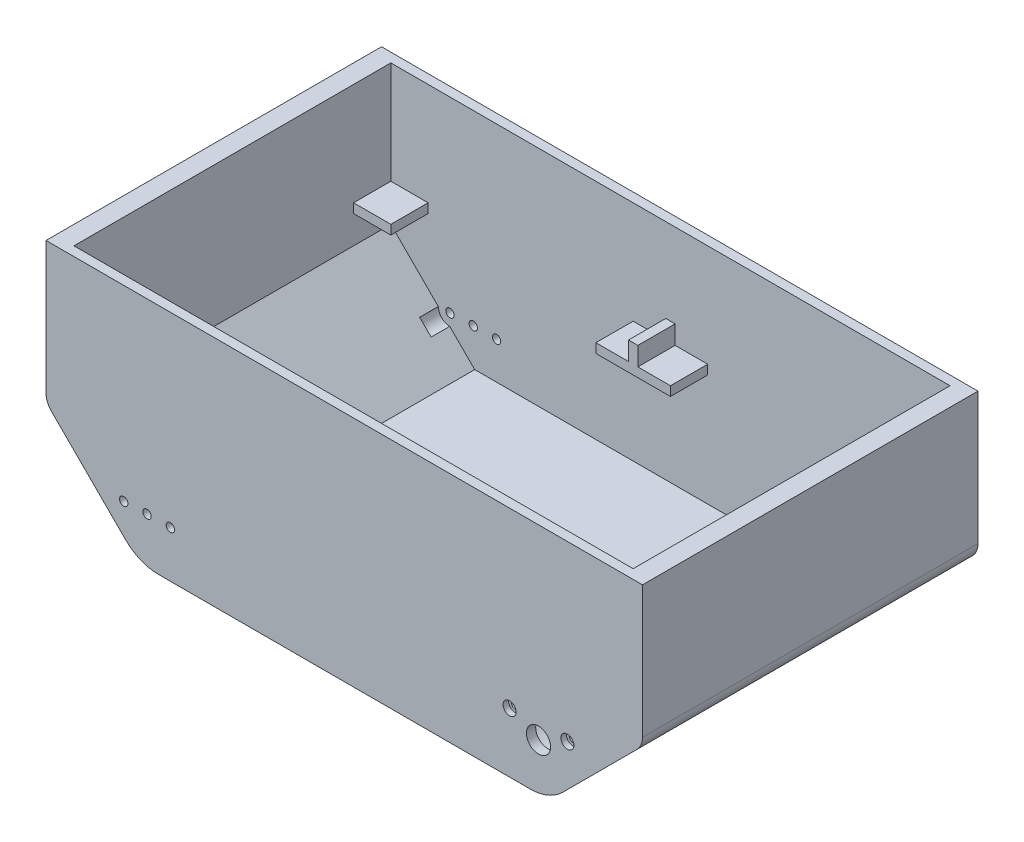
SolidWorks part; units mm, degrees
ref_plane "Front Plane" through (0, 0, 0) normal (0, 0, 1) x (1, 0, 0)
ref_plane "Top Plane" through (0, 0, 0) normal (0, 1, 0) x (1, 0, 0)
ref_plane "Right Plane" through (0, 0, 0) normal (1, 0, 0) x (0, 0, -1)
sketch "Sketch1" plane through (0, 0, 0) normal (0, 1, 0) x (1, 0, 0)
  line L1 (-160, -90) -> (160, -90)
  line L2 (-160, -90) -> (-160, 90)
  line L3 (-160, 90) -> (160, 90)
  line L4 (160, -90) -> (160, 90)
  line L5 (-160, -90) -> (160, 90) construction
  line L6 (-160, 90) -> (160, -90) construction
  point P0 (0, 0)
  dimension "D1" = 320
  dimension "D2" = 180
extrude "Boss-Extrude1" add sketch "Sketch1" along normal blind 50
sketch "Sketch2" plane through (0, 0, 90) normal (0, 0, 1) x (1, 0, 0)
  line L0 (-160, 50) -> (-110, 0)
  line L1 (-160, 0) -> (160, 0) construction
  line L2 (-110, 0) -> (-160, 0)
  line L3 (-160, 0) -> (-160, 50)
  dimension "D1" = 50
extrude "Cut-Extrude2" cut sketch "Sketch2" against normal through all
mirror "Mirror1" about plane through (0, 0, 0) normal (1, 0, 0) of "Cut-Extrude2"
ref_plane "Plane1" through (0, 0, 85) normal (0, 0, 1) x (1, 0, 0)
sketch "Sketch5" plane through (0, 0, 85) normal (0, 0, 1) x (1, 0, 0)
  line L1 (-150, 50) -> (150, 50)
  line L3 (-105, 5) -> (105, 5)
  line L5 (-160, 50) -> (160, 50) construction
  line L6 (-110, 0) -> (110, 0) construction
  line L8 (150, 50) -> (105, 5)
  line L9 (110, 0) -> (160, 50) construction
  line L10 (-150, 50) -> (-105, 5)
  line L11 (-110, 0) -> (-160, 50) construction
  dimension "D1" = 300
  dimension "D2" = 5
extrude "Cut-Extrude3" cut sketch "Sketch5" against normal blind 170
fillet "Fillet1" radius 25 2 edges at (110, 0, 0) (-110, 0, 0)
sketch "Sketch6" plane through (0, 0, -90) normal (0, 0, -1) x (-1, 0, 0)
  line L0 (99, 0) -> (-99, 0) construction
  circle A0 centre (-104.2117, 25) radius 6.5
  dimension "D1" = 13
  dimension "D2" = 25
extrude "Cut-Extrude4" cut sketch "Sketch6" against normal through all
sketch "Sketch11" plane through (0, 0, -90) normal (0, 0, -1) x (-1, 0, 0)
  circle A0 centre (-88.7117, 32) radius 2
  circle A1 centre (-104.2117, 25) radius 6.5 construction
  circle A2 centre (-119.7117, 32) radius 2
  dimension "D1" = 4
  dimension "D2" = 15.5
  dimension "D3" = 7
  dimension "D4" = 2
extrude "Cut-Extrude7" cut sketch "Sketch11" against normal through all
sketch "Sketch12" plane through (0, 0, -90) normal (0, 0, -1) x (-1, 0, 0)
  circle A0 centre (-88.7117, 32) radius 3.5
  circle A1 centre (-119.7117, 32) radius 3.5
  circle M1 centre (-88.7117, 32) radius 2
  dimension "D1" = 7
  dimension "D2" = 7
extrude "Cut-Extrude8" cut sketch "Sketch12" against normal blind 3 contours A0 M1 | A1 region at (92.1128, 32, -90)
mirror "Mirror3" about plane through (0, 0, 0) normal (0, 0, 1) of "Cut-Extrude8"
sketch "Sketch7" plane through (0, 0, -85) normal (0, 0, 1) x (1, 0, 0)
  line L0 (88.7117, 32) -> (119.7117, 32)
  circle A0 centre (104.2117, 32) radius 17.75
  dimension "D1" = 35.5
sketch "Sketch8" plane through (0, 0, -85) normal (0, 0, 1) x (1, 0, 0)
  line L0 (134.7756, 25) -> (113.989, 4.8879)
  line L3 (113.989, 4.8879) -> (73.1131, 4.8879)
  line L4 (73.1131, 25) -> (73.1131, 4.8879)
  line L5 (104.2117, 32) -> (73.1131, 4.8879) construction
  line L6 (122.5309, 13.1526) -> (104.2117, 32) construction
  line L9 (134.7756, 25) -> (73.1131, 25)
  point P0 (104.2117, 32)
extrude "Boss-Extrude2" add sketch "Sketch8" along normal blind 170 contours L4 L3 L0 L9
sketch "Sketch13" plane through (0, 0, -90) normal (0, 0, -1) x (-1, 0, 0)
  circle A0 centre (105.7883, 25) radius 2.25
  circle A1 centre (-104.2117, 25) radius 6.5 construction
  circle A2 centre (118.2883, 24.6397) radius 2.25
  circle A3 centre (93.2883, 25) radius 2.25
  dimension "D1" = 4.5
  dimension "D2" = 210
  dimension "D3" = 4.5
  dimension "D4" = 12.5
  dimension "D5" = 4.5
  dimension "D6" = 12.5
extrude "Cut-Extrude9" cut sketch "Sketch13" against normal through all
extrude "Cut-Extrude11" cut sketch "Sketch7" along normal blind 170 contours A0
sketch "Sketch14" plane through (0, 0, 85) normal (0, 0, -1) x (-1, 0, 0)
  line L0 (93.2883, 25) -> (118.2883, 24.6397) construction
  line L1 (93.3783, 31.2494) -> (118.3783, 30.889)
  line L2 (93.1982, 18.7506) -> (118.1982, 18.3903)
  arc A0 (93.3783, 31.2494) -> (93.1982, 18.7506) centre (93.2883, 25) ccw
  arc A1 (118.1982, 18.3903) -> (118.3783, 30.889) centre (118.2883, 24.6397) ccw
  circle A2 centre (118.2883, 24.6397) radius 2.25 construction
  point P4 (105.7883, 24.8198)
  dimension "D1" = 4
extrude "Cut-Extrude10" cut sketch "Sketch14" along normal blind 10
mirror "Mirror4" about plane through (0, 0, 0) normal (0, 0, 1) of "Cut-Extrude10"
fillet "Fillet2" radius 25 1 edges at (125, 25, 0)
sketch "Sketch15" plane through (0, 0, -85) normal (0, 0, 1) x (1, 0, 0)
  circle A0 centre (104.2117, 32) radius 18.75
  dimension "D1" = 37.5
extrude "Cut-Extrude12" cut sketch "Sketch15" along normal blind 50 contours A0
mirror "Mirror5" about plane through (0, 0, 0) normal (0, 0, 1) of "Cut-Extrude12"
sketch "Sketch16" plane through (0, 50, 0) normal (0, 1, 0) x (1, 0, 0)
  line L1 (-160, 90) -> (160, 90)
  line L2 (-160, 90) -> (-160, -90)
  line L3 (-160, -90) -> (160, -90)
  line L4 (160, 90) -> (160, -90)
  line L9 (150, 85) -> (-150, 85)
  line L10 (150, 85) -> (150, -85)
  line L11 (150, -85) -> (-150, -85)
  line L12 (-150, 85) -> (-150, -85)
  line L13 (160, 90) -> (-160, 90)
  line L14 (160, 90) -> (160, -90)
  line L15 (160, -90) -> (-160, -90)
  line L16 (-160, 90) -> (-160, -90)
  line M1 (-150, -85) -> (-150, 85)
  line M2 (-150, 85) -> (150, 85)
  line M3 (150, 85) -> (150, -85)
  line M4 (150, -85) -> (-150, -85)
  line M5 (160, -90) -> (160, 90)
  line M6 (160, 90) -> (-160, 90)
  line M7 (-160, 90) -> (-160, -90)
  line M8 (-160, -90) -> (160, -90)
extrude "Boss-Extrude4" add sketch "Sketch16" along normal blind 75 contours M8 M5 M6 M7 M4 M1 M2 M3 region at (0, 50, -86.3285)
fillet "Fillet3" radius 10 2 edges at (-160, 50, 0) (160, 50, 0)
ref_plane "Plane2" through (0, 65, 0) normal (0, 1, 0) x (1, 0, 0)
sketch "Sketch17" plane through (0, 65, 0) normal (0, 1, 0) x (1, 0, 0)
  line L0 (86.8174, 85) -> (73.1131, 85) construction
  line L1 (-150, 85) -> (-130, 85)
  line L2 (-150, 85) -> (-150, 65)
  line L3 (-150, 65) -> (-130, 65)
  line L4 (-130, 85) -> (-130, 65)
  line L7 (-150, 85) -> (-150, -85) construction
  point P8 (-150, 75)
  dimension "D1" = 20
  dimension "D2" = 20
extrude "Boss-Extrude5" add sketch "Sketch17" along normal blind 5
pattern_linear "LPattern1" count 2 spacing 150 along (0, 0, 1) count 2 spacing 130 along (1, 0, 0) of "Boss-Extrude5"
mirror "Mirror6" about plane through (0, 0, 0) normal (1, 0, 0) of "LPattern1"
sketch "Sketch18" plane through (0, 70, 0) normal (0, 1, 0) x (1, 0, 0)
  line L1 (-2.5, 65) -> (2.5, 65)
  line L3 (-2.5, 85) -> (2.5, 85)
  line L4 (2.5, 65) -> (2.5, 85)
  line L5 (20, 85) -> (-20, 85) construction
  line L6 (-2.5, 65) -> (-2.5, 85)
extrude "Boss-Extrude6" add sketch "Sketch18" along normal blind 10
mirror "Mirror7" about plane through (0, 0, 0) normal (0, 0, 1) of "Boss-Extrude6"
